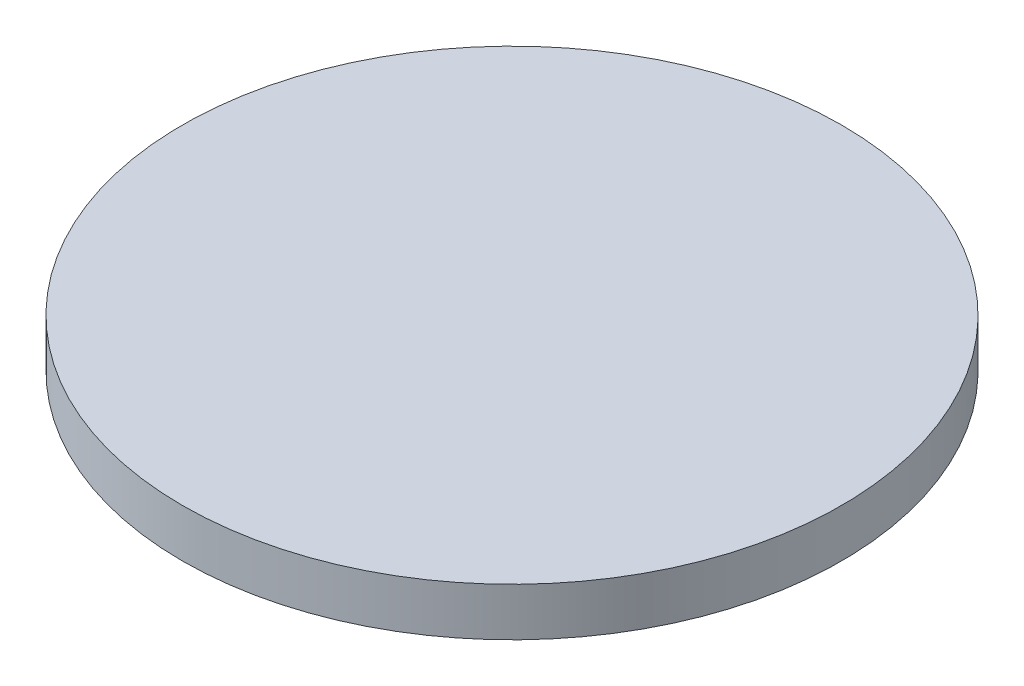
SolidWorks part; units mm, degrees
ref_plane "Front Plane" through (0, 0, 0) normal (0, 0, 1) x (1, 0, 0)
ref_plane "Top Plane" through (0, 0, 0) normal (0, 1, 0) x (1, 0, 0)
ref_plane "Right Plane" through (0, 0, 0) normal (1, 0, 0) x (0, 0, -1)
sketch "Sketch1" plane through (0, 0, 0) normal (0, 1, 0) x (1, 0, 0)
  circle A0 centre (0, 0) radius 21.75
  circle A1 centre (0, 0) radius 0.5
  dimension "D1" = 43.5
extrude "Boss-Extrude1" add sketch "Sketch1" along normal blind 3.175 contours A0
extrude "Cut-Extrude1" cut sketch "Sketch1<3>" along normal blind 1 contours A1
sketch "Sketch1<3>" plane through (0, 0, 0) normal (0, 1, 0) x (1, 0, 0) same geometry as "Sketch1"
